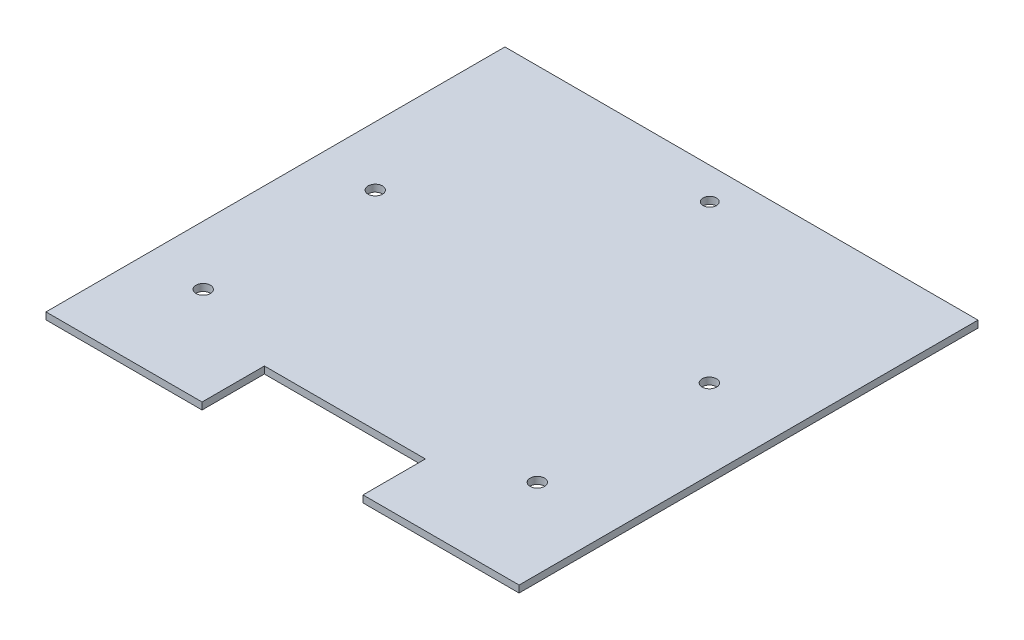
SolidWorks part; units mm, degrees
ref_plane "Front Plane" through (0, 0, 0) normal (0, 0, 1) x (1, 0, 0)
ref_plane "Top Plane" through (0, 0, 0) normal (0, 1, 0) x (1, 0, 0)
ref_plane "Right Plane" through (0, 0, 0) normal (1, 0, 0) x (0, 0, -1)
sketch "Sketch1" plane through (0, 0, 0) normal (0, 1, 0) x (1, 0, 0)
  line L1 (-94.869, -92.025) -> (94.869, -92.025)
  line L2 (-94.869, -92.025) -> (-94.869, 92.025)
  line L3 (-94.869, 92.025) -> (94.869, 92.025)
  line L4 (94.869, -92.025) -> (94.869, 92.025)
  line L5 (-94.869, -92.025) -> (94.869, 92.025) construction
  line L6 (-94.869, 92.025) -> (94.869, -92.025) construction
  point P0 (0, 0)
  dimension "D1" = 189.738
  dimension "D2" = 184.05
extrude "Boss-Extrude1" add sketch "Sketch1" along normal blind 2.794
sketch "Sketch2" plane through (0, 2.794, 0) normal (0, 1, 0) x (1, 0, 0)
  line L2 (94.869, 92.025) -> (-94.869, 92.025) construction
  circle A0 centre (0, 79.325) radius 2.6797
  point P4 (0, 92.025)
  dimension "D1" = 5.3594
  dimension "D2" = 12.7
extrude "Cut-Extrude1" cut sketch "Sketch2" against normal through all
sketch "Sketch3" plane through (0, 2.794, 0) normal (0, 1, 0) x (1, 0, 0)
  line L0 (0, -92.025) -> (-32.28, -92.025)
  line L1 (-94.869, -92.025) -> (94.869, -92.025) construction
  line L2 (-32.28, -92.025) -> (-32.28, -67.025)
  line L3 (-32.28, -67.025) -> (32.28, -67.025)
  line L4 (32.28, -67.025) -> (32.28, -92.025)
  line L5 (32.28, -92.025) -> (0, -92.025)
  point P5 (0, -67.025)
  dimension "D1" = 64.56
  dimension "D3" = 25
extrude "Cut-Extrude2" cut sketch "Sketch3" against normal through all
sketch "Sketch4" plane through (0, 2.794, 0) normal (0, 1, 0) x (1, 0, 0)
  line L0 (32.28, -67.025) -> (-32.28, -67.025) construction
  line L1 (-82.169, -60.675) -> (77.831, -60.675)
  line L2 (-82.169, -60.675) -> (-82.169, 29.325)
  line L3 (-82.169, 29.325) -> (77.831, 29.325)
  line L4 (77.831, -60.675) -> (77.831, 29.325)
  line L5 (-94.869, 92.025) -> (-94.869, -92.025) construction
  circle A1 centre (-71.169, -52.675) radius 2.8937
  circle A2 centre (-71.169, 16.325) radius 2.8937
  circle A4 centre (62.831, 16.325) radius 2.8937
  circle A5 centre (62.831, -52.675) radius 2.8937
  dimension "D5" = 5.7874
  dimension "D8" = 11
  dimension "D9" = 8
  dimension "D12" = 77
  dimension "D13" = 11
  dimension "D14" = 145
  dimension "D15" = 8
  dimension "D16" = 145
  dimension "D17" = 77
  dimension "D1" = 6.35
  dimension "D2" = 90
  dimension "D3" = 160
  dimension "D4" = 12.7
extrude "Cut-Extrude3" cut sketch "Sketch4" against normal through all contours A2 | A1 | A5 | A4
